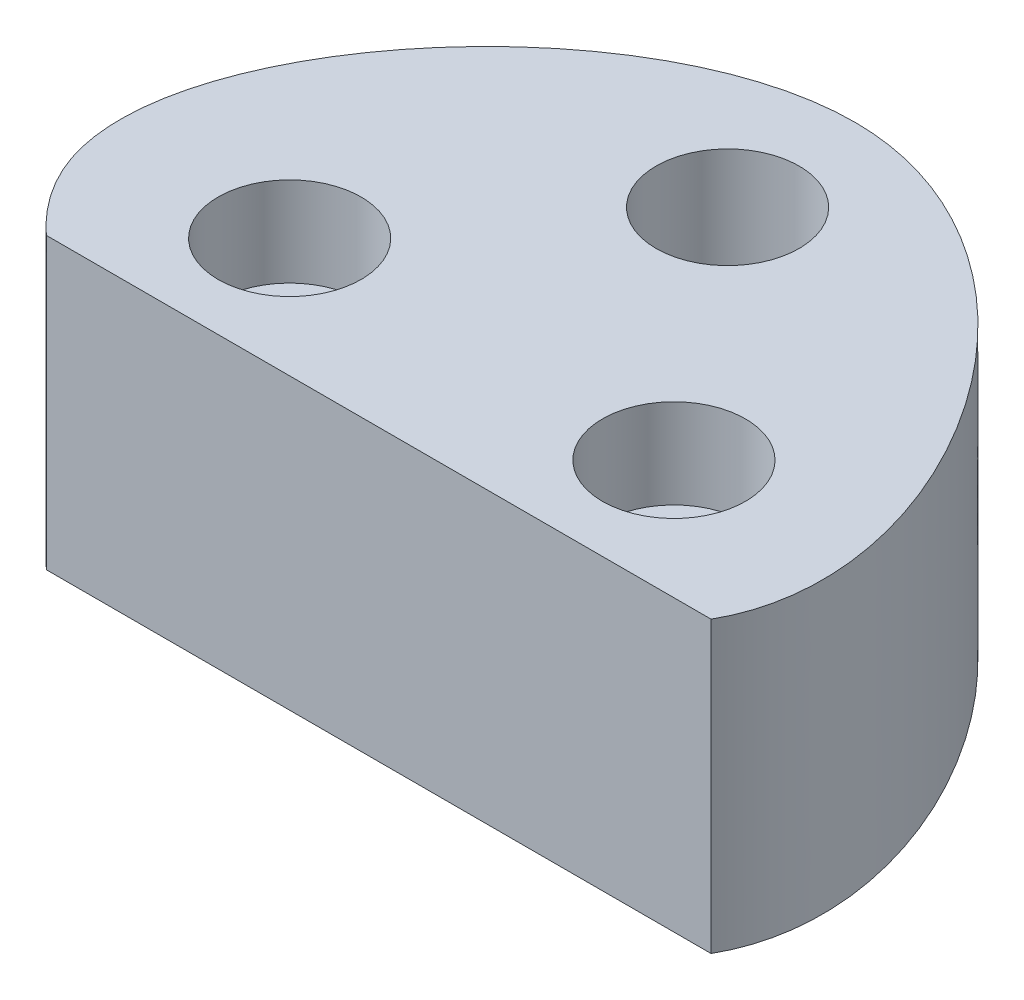
SolidWorks part; units mm, degrees
note: The reader was unsure of these and kept them because the rebuilt part matched: shared geometry of "Sketch10<5>".
ref_plane "Front Plane" through (0, 0, 0) normal (0, 0, 1) x (1, 0, 0)
ref_plane "Top Plane" through (0, 0, 0) normal (0, 1, 0) x (1, 0, 0)
ref_plane "Right Plane" through (0, 0, 0) normal (1, 0, 0) x (0, 0, -1)
sketch "Sketch2" plane through (0, 0, 0) normal (0, 1, 0) x (1, 0, 0)
  circle A0 centre (0, 0) radius 50
extrude "Boss-Extrude1" add sketch "Sketch2" along normal blind 16.2 contours A0
sketch "Sketch4" plane through (0, 16.2, 0) normal (0, 1, 0) x (1, 0, 0)
  circle A0 centre (0, 0) radius 4
  dimension "D1" = 8
sketch "Sketch7" plane through (0, 16.2, 0) normal (0, 1, 0) x (1, 0, 0)
  circle A0 centre (-10.75, -13.75) radius 4
  dimension "D1" = 8
extrude "Cut-Extrude2" cut sketch "Sketch7" against normal blind 5 contours A0
mirror "Mirror1" about plane through (0, 0, 0) normal (1, 0, 0) of "Cut-Extrude2"
extrude "Cut-Extrude3" cut sketch "Sketch4" against normal blind 18
sketch "Sketch10" plane through (0, 16.2, 0) normal (0, 1, 0) x (1, 0, 0)
  line L0 (-18.3895, -20.417) -> (19.4914, -20.417)
  line L1 (-18.3895, -20.417) -> (-18.3895, -33.817)
  line L2 (19.4914, -20.417) -> (19.4914, -33.817)
  line L3 (-18.3895, -33.817) -> (19.4914, -33.817)
  spline S0 degree 3 poles (38.7332, -33.4891) (1.6925, 24.281) (-39.7976, -25.754) (38.7332, -33.4891) (1.6925, 24.281) (-39.7976, -25.754) knots -1 -0.703327 -0.322215 0 0.296673 0.677785 1 1.296673 1.677785 2 only from (0, 7.6715) to (0, 7.6715)
  circle M4 centre (0, 0) radius 50
extrude "Cut-Extrude6" cut sketch "Sketch10" against normal blind 20 contours L0 S0 | S0 L0 L1 L3 L2 | S0 L2 L3 L1 L0 M4
extrude "Cut-Extrude7" cut sketch "Sketch10<5>" against normal blind 20 contours L0 S0 | S0 L0 L1 L3 L2
sketch "Sketch10<5>" plane through (0, 16.2, 0) normal (0, 1, 0) x (1, 0, 0) same geometry as "Sketch10"
